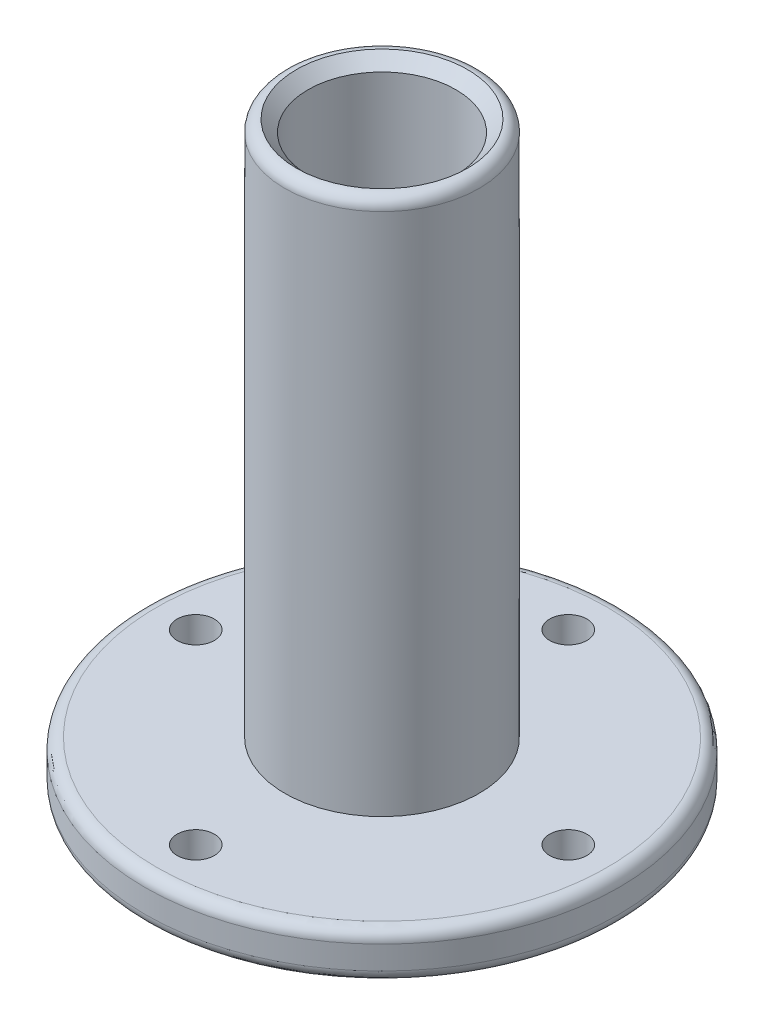
SolidWorks part; units mm, degrees
material "AISI 1035 Acier (SS)"
ref_plane "Plan de face" through (0, 0, 0) normal (0, 0, 1) x (1, 0, 0)
ref_plane "Plan de dessus" through (0, 0, 0) normal (0, 1, 0) x (1, 0, 0)
ref_plane "Plan de droite" through (0, 0, 0) normal (1, 0, 0) x (0, 0, -1)
sketch "Esquisse1" plane through (0, 0, 0) normal (0, 0, 1) x (1, 0, 0)
  line L0 (4.175, 32.2608) -> (4.175, 9.2608)
  line L1 (4.175, 9.2608) -> (10.175, 9.2608)
  line L2 (10.175, 9.2608) -> (10.175, 7.2608)
  line L9 (4.175, 32.2608) -> (3.175, 32.2608)
  line L10 (3.175, 32.2608) -> (3.175, 7.2608)
  line L11 (10.175, 7.2608) -> (3.175, 7.2608)
  line L12 (0, 0) -> (0, 15) construction
  dimension "D1" = 12.5
  dimension "D2" = 2
  dimension "D3" = 25
  dimension "D4" = 3.175
  dimension "D5" = 6
  dimension "D6" = 7
revolve "Révolution2" add sketch "Esquisse1" angle 360 about L12
fillet "Congé1" radius 0.5 3 edges at (0, 32.2608, -4.175) (0, 7.2608, -10.175) (0, 9.2608, -10.175)
chamfer "Chanfrein1" distance 0.5 angle 45 2 edges at (0, 7.2608, -3.175) (0, 32.2608, -3.175)
sketch "Esquisse8" plane through (0, 9.2608, 0) normal (0, 1, 0) x (1, 0, 0)
  circle A0 centre (8, 0) radius 0.8
  circle A4 centre (0, -8) radius 0.8
  circle A5 centre (-8, 0) radius 0.8
  circle A6 centre (0, 8) radius 0.8
  point P12 (0, 0)
  dimension "D1" = 1.6
  dimension "D3" = 4
  dimension "D2" = 8
extrude "Enlèv. mat.-Extru.2" cut sketch "Esquisse8" against normal through all
